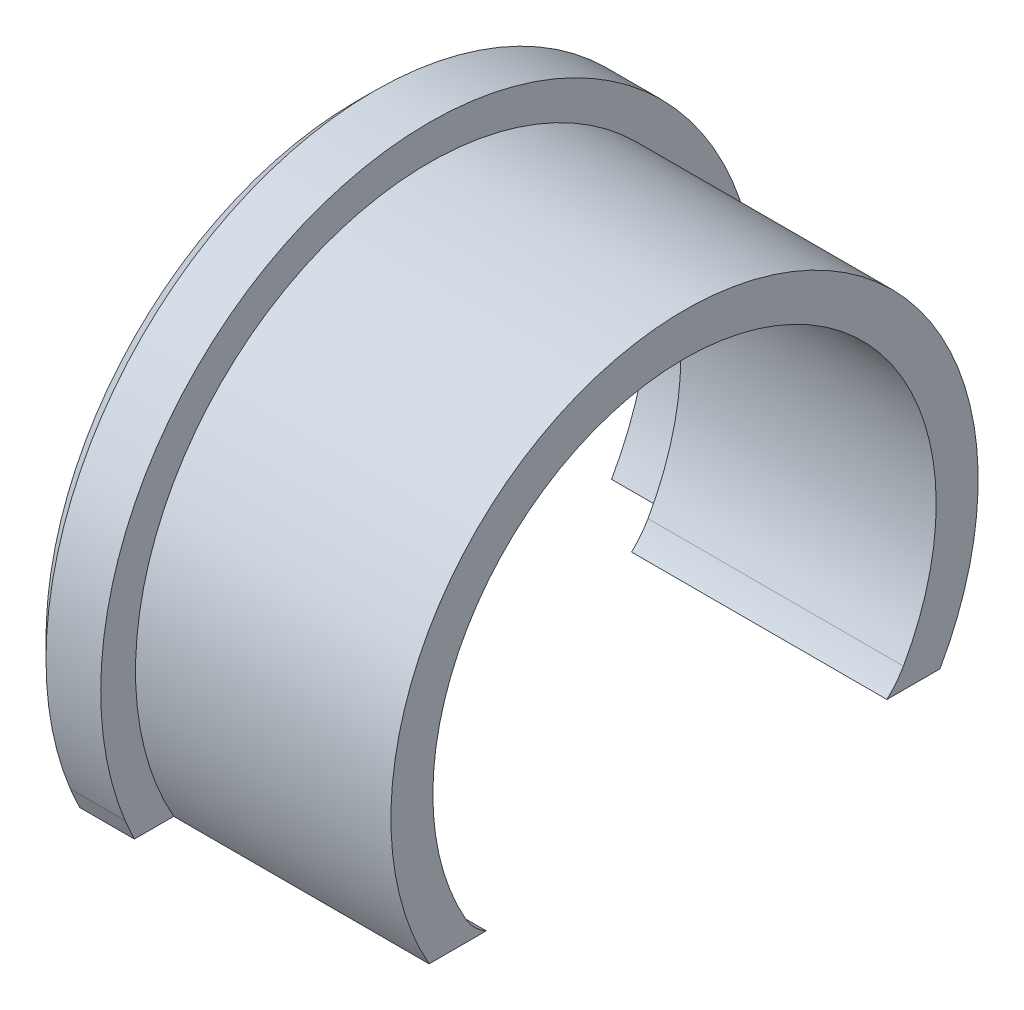
SolidWorks part; units mm, degrees
ref_plane "Front Plane" through (0, 0, 0) normal (0, 0, 1) x (1, 0, 0)
ref_plane "Top Plane" through (0, 0, 0) normal (0, 1, 0) x (1, 0, 0)
ref_plane "Right Plane" through (0, 0, 0) normal (1, 0, 0) x (0, 0, -1)
sketch "Sketch1" plane through (0, 0, 0) normal (1, 0, 0) x (0, 0, -1)
  line L0 (3.85, 0) -> (-3.85, 0) construction
  line L2 (0.5671, -0.5671) -> (-1, -0.5671)
  line L4 (11.5476, -0.5671) -> (13, -0.5671)
  arc A0 (0, 0) -> (12, 0) centre (6, 3.4024) cw
  arc A1 (-1, -0.5671) -> (13, -0.5671) centre (6, 3.4024) cw
  arc A2 (0, 0) -> (12, 0) centre (6, 3.4024) cw construction
  arc A3 (0, 0) -> (0.5671, -0.5671) centre (1.3098, 0.7428) ccw
  arc A4 (12, 0) -> (11.5476, -0.5671) centre (9.9884, 1.1407) cw
  point P3 (6, 10.3)
  dimension "D2" = 10.3
  dimension "D1" = 12
  dimension "D3" = 14
extrude "Boss-Extrude1" add sketch "Sketch1" along normal blind 7
sketch "Sketch6" plane through (0, 0, 0) normal (1, 0, 0) x (0, 0, -1)
  line L0 (-2.3321, 0) -> (-2.0773, -0.5671)
  line L1 (14.3321, 0) -> (14.0773, -0.5671)
  line L2 (14.0773, -0.5671) -> (13, -0.5671)
  line L3 (-2.0773, -0.5671) -> (-1, -0.5671)
  line L4 (-1, -0.5671) -> (13, -0.5671)
  line L5 (-2.3321, 0) -> (-2.0773, -0.5671)
  line L6 (3.85, 0) -> (-3.85, 0) construction
  line L8 (0.5671, -0.5671) -> (-4.5943, -0.5671) construction
  line L9 (-2.0773, -0.5671) -> (-1, -0.5671)
  line L10 (-1, -0.5671) -> (13, -0.5671)
  line L11 (14.0773, -0.5671) -> (13, -0.5671)
  line L12 (14.3321, 0) -> (14.0773, -0.5671)
  arc A0 (14.3321, 0) -> (-2.3321, 0) centre (6, 3.4024) ccw
  arc A12 (13, -0.5671) -> (-1, -0.5671) centre (6, 3.4024) ccw construction
  arc A13 (14.3321, 0) -> (-2.3321, 0) centre (6, 3.4024) ccw
  dimension "D2" = 9
  dimension "D3" = 9
  dimension "D4" = 0
  dimension "D1" = 9
extrude "Boss-Extrude3" add sketch "Sketch6" against normal blind 2 contours A13 L0 L3 L4 L2 L1
extrude "Cut-Extrude1" cut sketch "Sketch1<31>" along direction (1, 0, 0) on the side against the normal up to vertex (2 mm away) contours A0 A4 L4 A1 L2 A3 body kept at (7, -0.5671, 1) body kept at (0, 0, 2.3321) up to point (-2, -0.5671, 2.0773)
sketch "Sketch1<31>" plane through (0, 0, 0) normal (1, 0, 0) x (0, 0, -1) same geometry as "Sketch1"
chamfer "Chamfer1" distance 0.5 angle 45 1 edges at (-2, 12.4024, -6)
